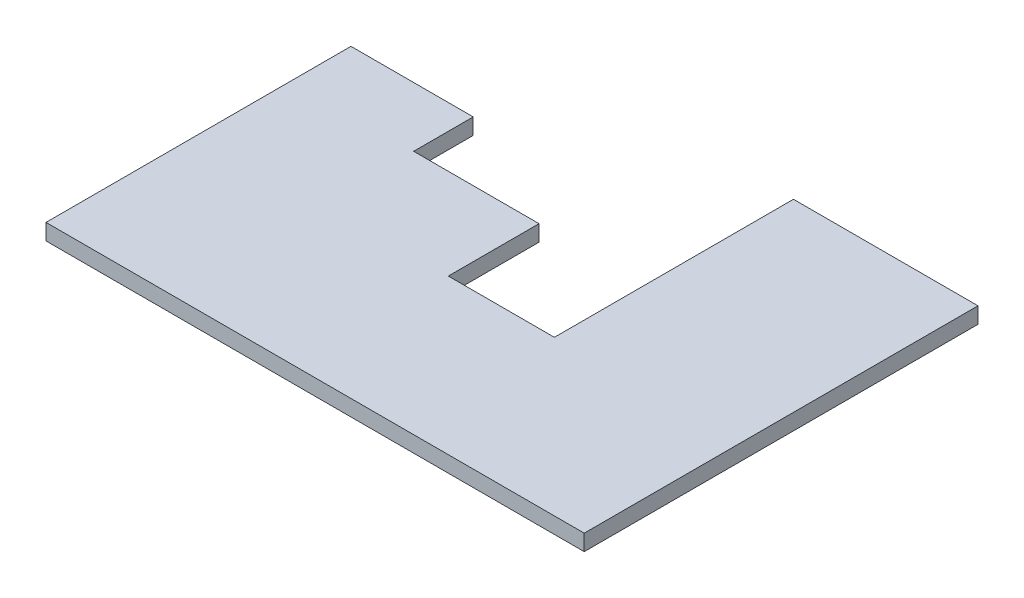
SolidWorks part; units mm, degrees
ref_plane "Front Plane" through (0, 0, 0) normal (0, 0, 1) x (1, 0, 0)
ref_plane "Top Plane" through (0, 0, 0) normal (0, 1, 0) x (1, 0, 0)
ref_plane "Right Plane" through (0, 0, 0) normal (1, 0, 0) x (0, 0, -1)
sketch "Sketch1" plane through (0, 0, 0) normal (0, 1, 0) x (1, 0, 0)
  line L0 (0, 0) -> (0, 55.08)
  line L1 (0, 55.08) -> (22.08, 55.08)
  line L2 (22.08, 55.08) -> (22.08, 44.3239)
  line L3 (22.08, 44.3239) -> (44.723, 44.3239)
  line L4 (44.723, 44.3239) -> (44.723, 27.9371)
  line L5 (44.723, 27.9371) -> (63.8814, 27.9371)
  line L6 (63.8814, 27.9371) -> (63.8814, 71.1171)
  line L7 (63.8814, 71.1171) -> (97.2076, 71.1171)
  line L8 (97.2076, 71.1171) -> (97.2076, 0)
  line L9 (97.2076, 0) -> (0, 0)
  dimension "D1" = 55.08
  dimension "D2" = 22.08
  dimension "D3" = 10.7561
  dimension "D4" = 22.643
  dimension "D5" = 16.3868
  dimension "D6" = 19.1584
  dimension "D7" = 43.18
  dimension "D8" = 33.3263
extrude "Boss-Extrude1" add sketch "Sketch1" along normal blind 2.9
sketch "Sketch2" plane through (0, 0, -27.9371) normal (0, 0, -1) x (-1, 0, 0)
  line L0 (-63.8814, 0) -> (-44.723, 0) construction
  line L1 (-46.6822, 0) -> (-61.9222, 0)
  line L2 (-46.6822, 0) -> (-46.6822, 1.45)
  line L3 (-46.6822, 1.45) -> (-61.9222, 1.45)
  line L4 (-61.9222, 0) -> (-61.9222, 1.45)
  line L5 (-63.8814, 2.9) -> (-63.8814, 0) construction
  line L6 (-44.723, 2.9) -> (-44.723, 0) construction
  line L7 (-63.8814, 2.9) -> (-44.723, 2.9) construction
  point P8 (-61.9222, 0.725)
  dimension "D1" = 1.9592
  dimension "D2" = 1.9592
  dimension "D3" = 1.45
extrude "Cut-Extrude1" cut sketch "Sketch2" against normal blind 1.45
fillet "Fillet2" radius 2.54 1 edges at (54.3022, 1.45, -26.4871)
